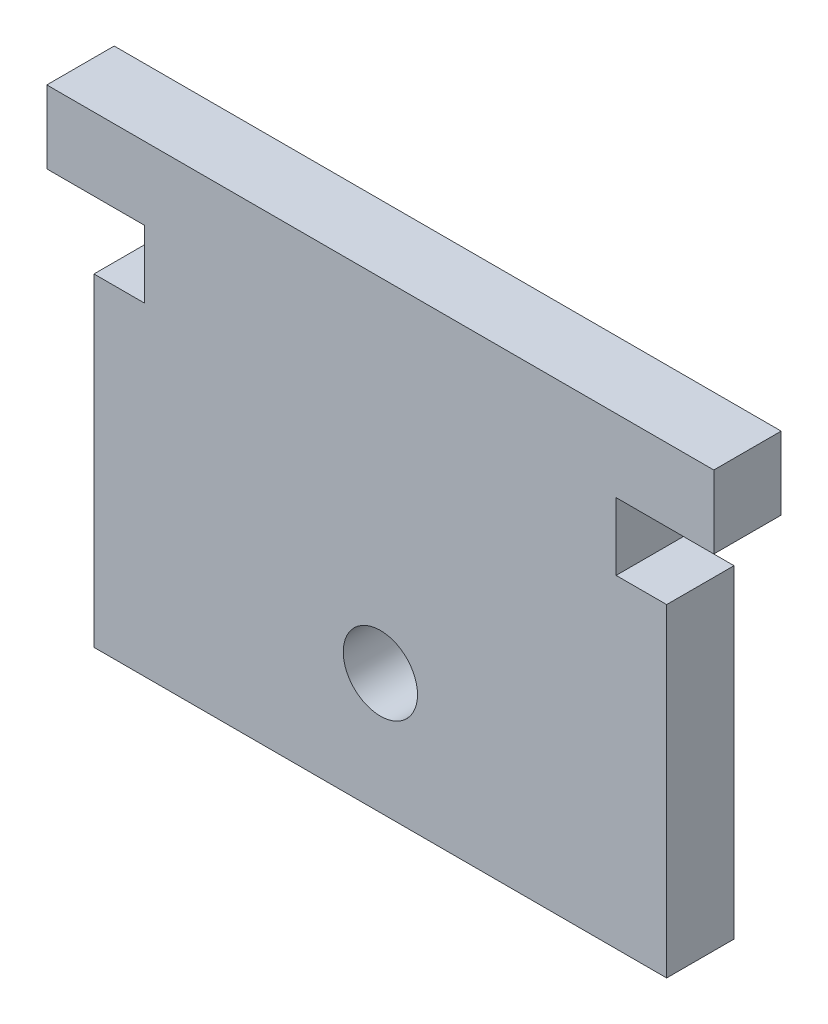
SolidWorks part; units mm, degrees
material "AISI 4130 Steel, annealed at 865C"
ref_plane "X-Y Datum" through (0, 0, 0) normal (0, 0, 1) x (1, 0, 0)
ref_plane "X-Z Datum" through (0, 0, 0) normal (0, 1, 0) x (1, 0, 0)
ref_plane "Y-Z Datum" through (0, 0, 0) normal (1, 0, 0) x (0, 0, -1)
sketch "Sketch1" plane through (0, 0, 0) normal (0, 0, 1) x (1, 0, 0)
  line L1 (-42.8625, -25.4) -> (42.8625, -25.4)
  line L2 (-42.8625, -25.4) -> (-42.8625, 25.4)
  line L3 (-42.8625, 25.4) -> (42.8625, 25.4)
  line L4 (42.8625, -25.4) -> (42.8625, 25.4)
  line L5 (-42.8625, -25.4) -> (42.8625, 25.4) construction
  line L6 (-42.8625, 25.4) -> (42.8625, -25.4) construction
  point P0 (0, 0)
  dimension "D1" = 85.725
  dimension "D2" = 50.8
extrude "Boss-Extrude1" add sketch "Sketch1" along normal blind 6.35
sketch "Sketch2" plane through (0, 0, 6.35) normal (0, 0, 1) x (1, 0, 0)
  line L1 (-42.8625, -25.4) -> (-26.9875, -25.4)
  line L2 (-42.8625, -25.4) -> (-42.8625, 17.78)
  line L3 (-42.8625, 17.78) -> (-26.9875, 17.78)
  line L4 (-26.9875, -25.4) -> (-26.9875, 17.78)
  line L5 (42.8625, -25.4) -> (26.9875, -25.4)
  line L6 (42.8625, -25.4) -> (42.8625, 17.78)
  line L7 (42.8625, 17.78) -> (26.9875, 17.78)
  line L8 (26.9875, -25.4) -> (26.9875, 17.78)
  dimension "D1" = 15.875
  dimension "D2" = 43.18
extrude "Cut-Extrude1" cut sketch "Sketch2" against normal blind 6.35
sketch "Sketch3" plane through (0, 25.4, 0) normal (0, 1, 0) x (1, 0, 0)
  line L1 (-42.8625, 0) -> (42.8625, 0)
  line L2 (-42.8625, 0) -> (-42.8625, -6.35)
  line L3 (-42.8625, -6.35) -> (42.8625, -6.35)
  line L4 (42.8625, 0) -> (42.8625, -6.35)
extrude "Cut-Extrude2" cut sketch "Sketch3" against normal blind 0.762
sketch "Sketch5" plane through (-26.9875, 0, 0) normal (-1, 0, 0) x (0, 0, 1)
  line L0 (6.35, -25.4) -> (6.35, 17.78) construction
  line L1 (0, 17.78) -> (6.35, 17.78)
  line L2 (0, 17.78) -> (0, 11.43)
  line L3 (0, 11.43) -> (6.35, 11.43)
  line L4 (6.35, 17.78) -> (6.35, 11.43)
  dimension "D1" = 6.35
extrude "Cut-Extrude3" cut sketch "Sketch5" against normal blind 4.7625
mirror "Mirror1" about plane through (0, 0, 0) normal (1, 0, 0) of "Cut-Extrude3"
sketch "Sketch6" plane through (0, 0, 6.35) normal (0, 0, 1) x (1, 0, 0)
  line L12 (26.9875, 11.43) -> (22.225, 11.43)
  line L13 (22.225, 11.43) -> (22.225, 17.78)
  line L14 (22.225, 17.78) -> (42.8625, 17.78)
  line L15 (42.8625, 17.78) -> (42.8625, 24.638)
  line L16 (42.8625, 24.638) -> (-42.8625, 24.638)
  line L17 (-42.8625, 24.638) -> (-42.8625, 17.78)
  line L18 (-42.8625, 17.78) -> (-22.225, 17.78)
  line L19 (-22.225, 17.78) -> (-22.225, 11.43)
  line L20 (-22.225, 11.43) -> (-26.9875, 11.43)
  line L21 (-26.9875, 11.43) -> (-26.9875, -25.4)
  line L22 (-26.9875, -25.4) -> (26.9875, -25.4)
  line L23 (26.9875, -25.4) -> (26.9875, 11.43)
  line L24 (26.9875, 11.43) -> (22.225, 11.43)
  line L25 (22.225, 11.43) -> (22.225, 17.78)
  line L26 (22.225, 17.78) -> (42.8625, 17.78)
  line L27 (42.8625, 17.78) -> (42.8625, 24.638)
  line L28 (42.8625, 24.638) -> (-42.8625, 24.638)
  line L29 (-42.8625, 24.638) -> (-42.8625, 17.78)
  line L30 (-42.8625, 17.78) -> (-22.225, 17.78)
  line L31 (-22.225, 17.78) -> (-22.225, 11.43)
  line L32 (-22.225, 11.43) -> (-26.9875, 11.43)
  line L33 (-26.9875, 11.43) -> (-26.9875, -25.4)
  line L34 (-26.9875, -25.4) -> (26.9875, -25.4)
  line L35 (26.9875, -25.4) -> (26.9875, 11.43)
  circle A1 centre (0.0059, -7.6663) radius 3.5
  dimension "D2" = 17.7337
  dimension "D1" = 0
sketch "Sketch7" plane through (-42.8625, 0, 0) normal (-1, 0, 0) x (0, 0, 1)
  line L1 (0, 24.638) -> (6.35, 24.638)
  line L2 (0, 24.638) -> (0, 17.78)
  line L3 (0, 17.78) -> (6.35, 17.78)
  line L4 (6.35, 24.638) -> (6.35, 17.78)
extrude "Cut-Extrude5" cut sketch "Sketch7" against normal blind 11.43
mirror "Mirror2" about plane through (0, 0, 0) normal (1, 0, 0) of "Cut-Extrude5"
sketch "Sketch8" plane through (0, -25.4, 0) normal (0, -1, 0) x (1, 0, 0)
  line L7 (-26.9875, 6.35) -> (26.9875, 6.35)
  line L8 (-26.9875, 6.35) -> (-26.9875, 0)
  line L9 (-26.9875, 0) -> (26.9875, 0)
  line L10 (26.9875, 6.35) -> (26.9875, 0)
extrude "Cut-Extrude6" cut sketch "Sketch8" against normal blind 6.35
hole_wizard "M6 Clearance Hole1" positions "Sketch11" profile "Sketch10" hole size "M6" standard "ANSI Metric" end condition through all
sketch "Sketch11" plane through (0, 0, 6.35) normal (0, 0, 1) x (1, 0, 0)
  point P0 (0.0059, -7.6663)
sketch "Sketch10" plane through (0.0059, -7.6663, 6.35) normal (1, 0, 0) x (0, -1, 0)
  line L0 (0, 0) -> (0, 6.35)
  line L1 (0, 6.35) -> (3.5, 6.35)
  line L2 (3.5, 6.35) -> (3.5, 0)
  line L5 (3.5, 0) -> (0, 0)
  line L11 (0, -6.35) -> (0, 107.95) construction
  dimension "Thru Hole Dia." = 7
  dimension "Thru Hole Depth" = 6.35
